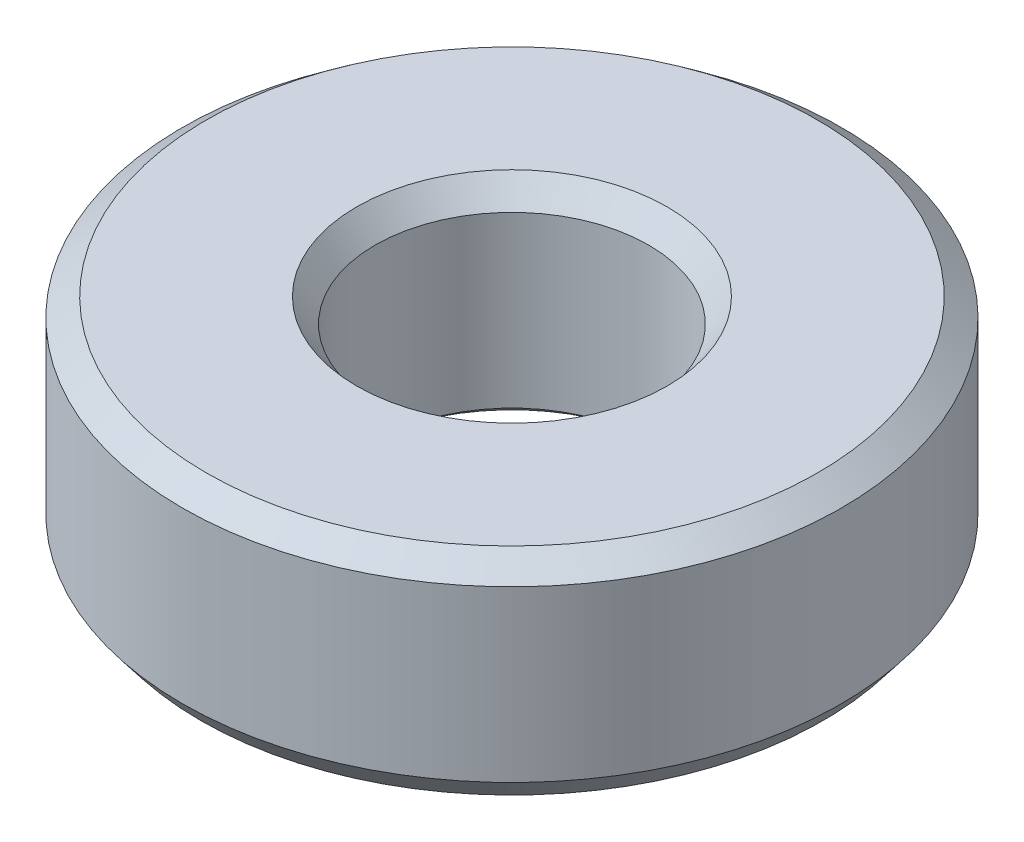
SolidWorks part; units mm, degrees
ref_plane "Front Plane" through (0, 0, 0) normal (0, 0, 1) x (1, 0, 0)
ref_plane "Top Plane" through (0, 0, 0) normal (0, 1, 0) x (1, 0, 0)
ref_plane "Right Plane" through (0, 0, 0) normal (1, 0, 0) x (0, 0, -1)
sketch "Sketch1" plane through (0, 0, 0) normal (0, 1, 0) x (1, 0, 0)
  circle A0 centre (0, 0) radius 17.5
  dimension "SLEEVE_OD" = 35
extrude "Boss-Extrude1" add sketch "Sketch1" along normal blind 11.2479
sketch "Sketch2" plane through (0, 0, 0) normal (0, 1, 0) x (1, 0, 0)
  circle A0 centre (0, 0) radius 7.2646
  dimension "BORE_D" = 14.5293
extrude "Cut-Extrude1" cut sketch "Sketch2" along normal through all
chamfer "Chamfer1" distance 0.9785 angle 52.376 4 edges at (0, 11.2479, 7.2646) (0, 0, 7.2646) (0, 0, 17.5) (0, 11.2479, 17.5) first distance on face at (0, 11.2479, 7.2646) first distance on face at (0, 0, 7.2646) first distance on face at (0, 11.2479, 17.5)
